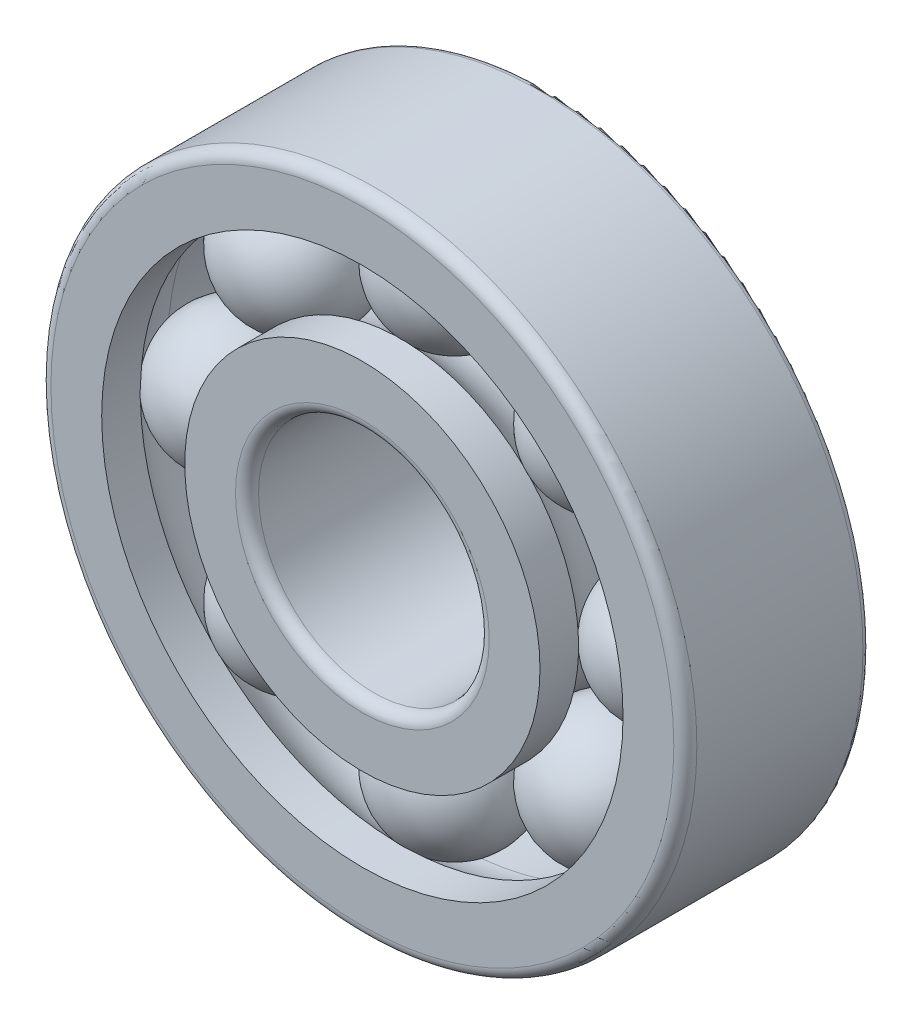
SolidWorks part; units mm, degrees
ref_plane "Front Plane" through (0, 0, 0) normal (0, 0, 1) x (1, 0, 0)
ref_plane "Top Plane" through (0, 0, 0) normal (0, 1, 0) x (1, 0, 0)
ref_plane "Right Plane" through (0, 0, 0) normal (1, 0, 0) x (0, 0, -1)
sketch "BaseSke" plane through (0, 0, 0) normal (1, 0, 0) x (0, 0, -1)
  line L0 (-47.2296, 0) -> (24.6132, 0) construction
  line L1 (-47.2296, 9.5) -> (24.6132, 9.5) construction
  line L2 (0, 129.5214) -> (0, -86.3012) construction
  line L3 (0, 12.45) -> (0, 6.55)
  line L4 (-4, 14) -> (4, 14) construction
  line L5 (-4, 5) -> (4, 5) construction
  arc A0 (0, 12.45) -> (0, 6.55) centre (0, 9.5) ccw
  dimension "D1" = 9.5
revolve "Ball" add sketch "BaseSke" angle 360 about L3
sketch "OuterRaceSke" plane through (0, 0, 0) normal (1, 0, 0) x (0, 0, -1)
  line L0 (0, 0) -> (0, 87.5396) construction
  line L1 (-4, 14) -> (4, 14)
  line L2 (-4, 14) -> (-4, 11.3)
  line L3 (-4, 11.3) -> (-2.3246, 11.3)
  line L4 (4, 14) -> (4, 12.44)
  line L5 (-50.3916, 0) -> (55.2197, 0) construction
  line L6 (-47.2296, 9.5) -> (24.6132, 9.5) construction
  line L7 (0, 12.44) -> (4, 12.44)
  arc A0 (0, 12.44) -> (-2.3246, 11.3) centre (0, 9.5) ccw
  dimension "D2" = 24.88
revolve "OuterRace" add sketch "OuterRaceSke" angle 360 about L5
sketch "InnerRaceSke" plane through (0, 0, 0) normal (1, 0, 0) x (0, 0, -1)
  line L0 (-70.8626, 0) -> (113.5527, 0) construction
  line L1 (0, 58.441) -> (0, -70.8113) construction
  line L2 (-4, 5) -> (4, 5)
  line L3 (-4, 5) -> (-4, 7.7)
  line L4 (-4, 7.7) -> (-2.3246, 7.7)
  line L5 (4, 5) -> (4, 7.7)
  line L6 (0, 129.5214) -> (0, -86.3012) construction
  line L7 (2.3246, 7.7) -> (4, 7.7)
  line L8 (-4, 14) -> (-4, 11.3) construction
  arc A0 (-2.3246, 7.7) -> (2.3246, 7.7) centre (0, 9.5) ccw
  arc A1 (0, 12.45) -> (0, 6.55) centre (0, 9.5) ccw construction
  arc A2 (0, 12.44) -> (-2.3246, 11.3) centre (0, 9.5) ccw construction
revolve "InnerRace" add sketch "InnerRaceSke" angle 360 about L0
fillet "Fillet1" radius 0.5 3 edges at (5, 0, -4) (5, 0, 4) (14, 0, 4)
fillet "Fillet2" radius 0.3 1 edges at (14, 0, -4)
pattern_circular "CirPatternBall" count 8 over 360 about axis through (0, 0, 50.3916) along (0, 0, -1) of "Ball"
sketch "SimplifiedSke" plane through (0, 0, 0) normal (1, 0, 0) x (0, 0, -1)
  line L0 (37.5911, 0) -> (-37.5911, 0) construction
  circle A0 centre (0, 9.5) radius 2.95
  arc A1 (0, 12.45) -> (0, 6.55) centre (0, 9.5) ccw construction
revolve "Simplified" [suppressed] add sketch "SimplifiedSke" angle 360 about L0
equation "\"D1@BaseSke\" =  (\"Bearing_Outside_Diameter@BaseSke\"  +  \"Bearing_Inside_Diameter@BaseSke\"  )  / 4"
equation "\"D2@OuterRaceSke\" = \"Ball_Outer_Diameter@BaseSke\"-0.02"
equation "\"D1@CirPatternBall\" =  int(  pi  * ( \"Bearing_Outside_Diameter@BaseSke\" + \"Bearing_Inside_Diameter@BaseSke\" )  / 2  / \"Bearing_Thickness@BaseSke\"*1.25) -1"
